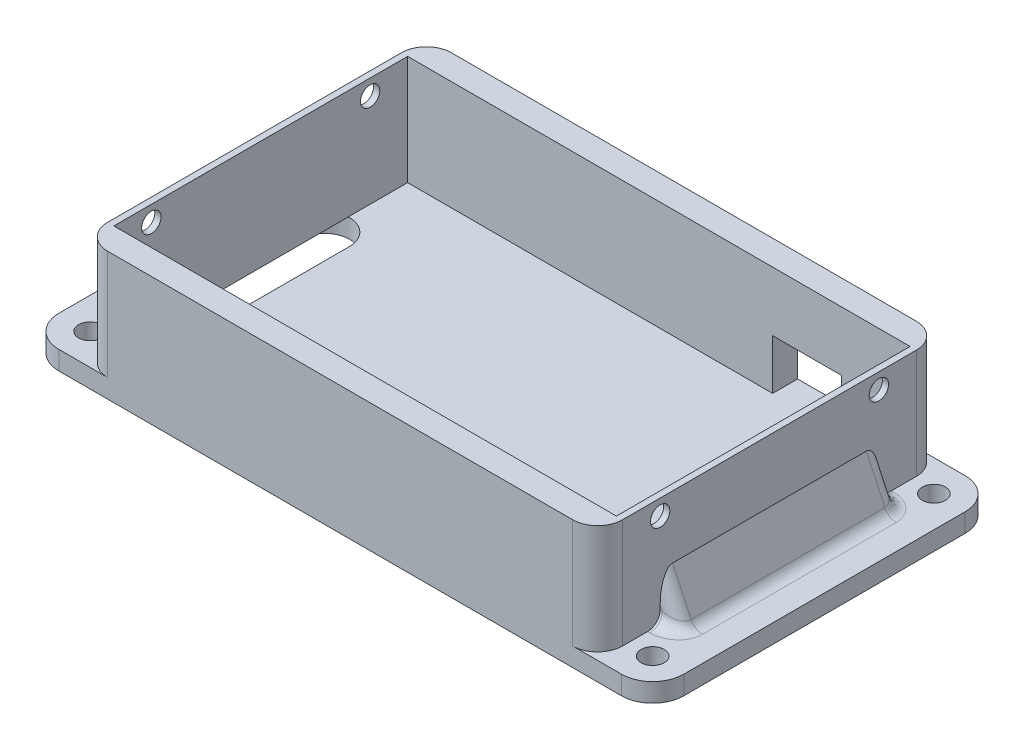
SolidWorks part; units mm, degrees
material "Copper"
ref_plane "Front Plane" through (0, 0, 0) normal (0, 0, 1) x (1, 0, 0)
ref_plane "Top Plane" through (0, 0, 0) normal (0, 1, 0) x (1, 0, 0)
ref_plane "Right Plane" through (0, 0, 0) normal (1, 0, 0) x (0, 0, -1)
sketch "Sketch1" plane through (0, 0, 0) normal (0, 1, 0) x (1, 0, 0)
  line L1 (6.35, 0) -> (120.65, 0)
  line L2 (0, 6.35) -> (0, 63.5)
  line L3 (6.35, 69.85) -> (120.65, 69.85)
  line L4 (127, 6.35) -> (127, 63.5)
  arc A0 (6.35, 0) -> (0, 6.35) centre (6.35, 6.35) cw
  arc A1 (120.65, 0) -> (127, 6.35) centre (120.65, 6.35) ccw
  arc A2 (120.65, 69.85) -> (127, 63.5) centre (120.65, 63.5) cw
  arc A3 (0, 63.5) -> (6.35, 69.85) centre (6.35, 63.5) cw
  point P7 (0, 0)
  point P10 (127, 0)
  point P13 (127, 69.85)
  point P16 (0, 69.85)
  dimension "D3" = 6.35
  dimension "D1" = 127
  dimension "D2" = 69.85
extrude "Base Extrude" add sketch "Sketch1" along normal blind 3.81
sketch "Sketch2" plane through (0, 3.81, 0) normal (0, 1, 0) x (1, 0, 0)
  line L0 (63.5, 69.85) -> (63.5, 0) construction
  line L1 (120.65, 69.85) -> (6.35, 69.85) construction
  line L2 (6.35, 0) -> (120.65, 0) construction
  line L3 (0, 34.925) -> (127, 34.925) construction
  line L4 (0, 63.5) -> (0, 6.35) construction
  line L5 (127, 6.35) -> (127, 63.5) construction
  line L6 (7.62, 34.925) -> (17.78, 34.925) construction
  line L8 (7.62, 47.625) -> (7.62, 22.225)
  line L10 (17.78, 47.625) -> (17.78, 22.225)
  line L11 (119.38, 47.625) -> (119.38, 22.225)
  line L12 (109.22, 47.625) -> (109.22, 22.225)
  circle A0 centre (6.35, 63.5) radius 2.3495
  circle A1 centre (6.35, 6.35) radius 2.3495
  arc A2 (17.78, 47.625) -> (7.62, 47.625) centre (12.7, 47.625) ccw
  arc A3 (7.62, 22.225) -> (17.78, 22.225) centre (12.7, 22.225) ccw
  circle A4 centre (120.65, 6.35) radius 2.3495
  circle A5 centre (120.65, 63.5) radius 2.3495
  arc A6 (109.22, 47.625) -> (119.38, 47.625) centre (114.3, 47.625) cw
  arc A7 (119.38, 22.225) -> (109.22, 22.225) centre (114.3, 22.225) cw
  dimension "D1" = 4.699
  dimension "D5" = 5.08
  dimension "D2" = 6.35
  dimension "D3" = 6.35
  dimension "D4" = 6.35
  dimension "D6" = 10.16
  dimension "D7" = 25.4
  dimension "D8" = 12.7
extrude "Hole Cuts" cut sketch "Sketch2" against normal through all
sketch "Sketch3" plane through (0, 3.81, 0) normal (0, 1, 0) x (1, 0, 0)
  line L0 (120.65, 69.85) -> (6.35, 69.85) construction
  line L1 (16.256, 69.85) -> (110.744, 69.85)
  line L2 (11.176, 64.77) -> (11.176, 5.08)
  line L3 (16.256, 0) -> (110.744, 0)
  line L4 (115.824, 64.77) -> (115.824, 5.08)
  line L5 (6.35, 0) -> (120.65, 0) construction
  line L6 (63.5, 69.85) -> (63.5, 0) construction
  line L7 (63.5, 0) -> (63.5, 69.85) construction
  line L9 (12.446, 64.77) -> (114.554, 64.77)
  line L10 (12.446, 64.77) -> (12.446, 5.08)
  line L11 (12.446, 5.08) -> (114.554, 5.08)
  line L12 (114.554, 64.77) -> (114.554, 5.08)
  arc A0 (110.744, 69.85) -> (115.824, 64.77) centre (110.744, 64.77) cw
  arc A1 (110.744, 0) -> (115.824, 5.08) centre (110.744, 5.08) ccw
  arc A2 (11.176, 5.08) -> (16.256, 0) centre (16.256, 5.08) ccw
  arc A3 (16.256, 69.85) -> (11.176, 64.77) centre (16.256, 64.77) ccw
  point P18 (115.824, 0)
  point P23 (11.176, 69.85)
  dimension "D6" = 5.08
  dimension "D1" = 104.648
  dimension "D2" = 1.27
  dimension "D3" = 1.27
  dimension "D4" = 5.08
  dimension "D5" = 5.08
extrude "Shell Extrude" add sketch "Sketch3" along normal blind 22.225
ref_plane "Shell Support Plane" through (0, 0, -34.925) normal (0, 0, 1) x (1, 0, 0)
sketch "Sketch4" plane through (0, 0, -34.925) normal (0, 0, 1) x (1, 0, 0)
  line L0 (11.176, 3.81) -> (6.731, 3.81)
  line L1 (6.731, 3.81) -> (11.176, 13.335)
  line L2 (11.176, 26.035) -> (11.176, 3.81) construction
  line L3 (11.176, 13.335) -> (11.176, 3.81)
  line L5 (63.5, 26.035) -> (63.5, 0) construction
  line L6 (16.256, 26.035) -> (110.744, 26.035) construction
  line L7 (6.35, 0) -> (120.65, 0) construction
  line L8 (115.824, 13.335) -> (115.824, 3.81)
  line L9 (120.269, 3.81) -> (115.824, 13.335)
  line L10 (115.824, 3.81) -> (120.269, 3.81)
  dimension "D1" = 4.445
  dimension "D2" = 9.525
extrude "Shell Support Extrude" add sketch "Sketch4" along normal blind 22.225 and the other way blind 22.225
fillet "Shell Support Fillet" radius 2.54 10 edges at (6.731, 3.81, -34.925) (8.9535, 3.81, -12.7) (8.9535, 8.5725, -12.7) (8.9535, 8.5725, -57.15) (8.9535, 3.81, -57.15) (118.0465, 8.5725, -57.15) (118.0465, 8.5725, -12.7) (118.0465, 3.81, -12.7) (120.269, 3.81, -34.925) (118.0465, 3.81, -57.15)
sketch "Sketch5" plane through (115.824, 0, 0) normal (1, 0, 0) x (0, 0, -1)
  line L0 (34.925, 26.035) -> (34.925, 0) construction
  line L1 (5.08, 26.035) -> (64.77, 26.035) construction
  line L2 (6.35, 0) -> (63.5, 0) construction
  line L3 (0, 26.035) -> (0, 3.81) construction
  circle A0 centre (12.7, 22.86) radius 1.9685
  circle A2 centre (57.15, 22.86) radius 1.9685
  dimension "D1" = 3.937
  dimension "D2" = 3.175
  dimension "D3" = 12.7
extrude "Cover Holes" cut sketch "Sketch5" against normal through all
sketch "Sketch6" plane through (0, 0, -69.85) normal (0, 0, -1) x (-1, 0, 0)
  line L0 (-120.65, 3.81) -> (-110.744, 3.81) construction
  line L1 (-100.584, 3.81) -> (-86.614, 3.81)
  line L2 (-100.584, 3.81) -> (-100.584, 13.97)
  line L3 (-100.584, 13.97) -> (-86.614, 13.97)
  line L4 (-86.614, 3.81) -> (-86.614, 13.97)
  line L5 (-110.744, 26.035) -> (-110.744, 3.81) construction
  dimension "D1" = 10.16
  dimension "D2" = 13.97
  dimension "D3" = 10.16
extrude "Cut-Extrude1" cut sketch "Sketch6" against normal up to next
